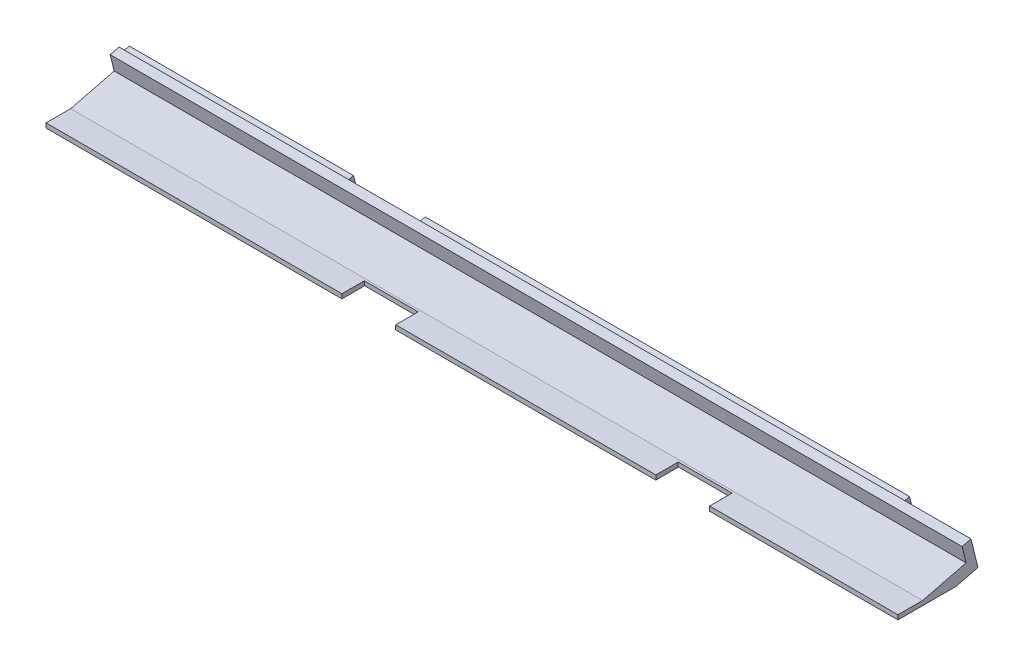
SolidWorks part; units mm, degrees
ref_plane "Front Plane" through (0, 0, 0) normal (0, 0, 1) x (1, 0, 0)
ref_plane "Top Plane" through (0, 0, 0) normal (0, 1, 0) x (1, 0, 0)
ref_plane "Right Plane" through (0, 0, 0) normal (1, 0, 0) x (0, 0, -1)
sketch "Sketch1" plane through (0, 0, 0) normal (1, 0, 0) x (0, 0, -1)
  line L0 (0, 0) -> (13, 0)
  line L1 (0, 0) -> (0, 1)
  line L2 (0, 1) -> (5.5, 1)
  line L3 (5.5, 1) -> (15.203, 3.4192)
  line L4 (13, 0) -> (19.7921, 1.6935)
  line L5 (19.7921, 1.6935) -> (18.5825, 6.5449)
  line L6 (15.203, 3.4192) -> (14.3041, 7.0241)
  line L7 (14.3041, 7.0241) -> (16.279, 7.5165)
  line L8 (16.279, 7.5165) -> (16.6419, 6.0611)
  line L9 (16.6419, 6.0611) -> (18.5825, 6.5449)
  dimension "D1" = 13
  dimension "D2" = 1
  dimension "D3" = 5.5
  dimension "D4" = 10
  dimension "D5" = 194
  dimension "D6" = 7
  dimension "D7" = 5
  dimension "D8" = 1.5
  dimension "D9" = 2
extrude "Profile" add sketch "Sketch1" along normal blind 190
sketch "Sketch2" plane through (0, 4.745, -19.0312) normal (0, 0.2419, -0.9703) x (-1, 0, 0)
  line L0 (-190, -3.145) -> (0, -3.145) construction
  line L1 (-188, -3.145) -> (-2, -3.145)
  line L2 (-188, -3.145) -> (-188, -1.145)
  line L3 (-188, -1.145) -> (-2, -1.145)
  line L4 (-2, -3.145) -> (-2, -1.145)
  line L5 (0, -3.145) -> (0, 1.855) construction
  line L6 (-190, -3.145) -> (-190, 1.855) construction
  dimension "D1" = 2
  dimension "D2" = 2
  dimension "D3" = 2
extrude "Air inlet" cut sketch "Sketch2" against normal through all
sketch "Bottom tab cuts" plane through (0, 1, 0) normal (0, 1, 0) x (1, 0, 0)
  line L0 (190, 0) -> (0, 0) construction
  line L1 (148, 0) -> (136, 0)
  line L2 (148, 0) -> (148, 5)
  line L3 (148, 5) -> (136, 5)
  line L4 (136, 0) -> (136, 5)
  line L5 (190, 5.5) -> (190, 0) construction
  line L8 (78, 0) -> (66, 0)
  line L9 (78, 0) -> (78, 5)
  line L10 (78, 5) -> (66, 5)
  line L11 (66, 0) -> (66, 5)
  dimension "D1" = 42
  dimension "D2" = 12
  dimension "D3" = 5
  dimension "D4" = 112
extrude "Bottom tabs" cut sketch "Bottom tab cuts" against normal blind 14
sketch "Sketch5" plane through (0, 1.7999, 0.4488) normal (0, 0.9703, 0.2419) x (1, 0, 0)
  line L0 (190, 17.6138) -> (0, 17.6138) construction
  line L1 (190, 19.6138) -> (174, 19.6138)
  line L2 (190, 19.6138) -> (190, 17.6138)
  line L3 (190, 17.6138) -> (174, 17.6138)
  line L4 (174, 19.6138) -> (174, 17.6138)
  line L5 (190, 19.6138) -> (0, 19.6138) construction
  line L6 (66, 19.6138) -> (50, 19.6138)
  line L7 (66, 19.6138) -> (66, 17.6138)
  line L8 (66, 17.6138) -> (50, 17.6138)
  line L9 (50, 19.6138) -> (50, 17.6138)
  line L10 (190, 17.6138) -> (0, 17.6138) construction
  dimension "D1" = 16
  dimension "D2" = 124
extrude "Cut-Extrude3" cut sketch "Sketch5" against normal blind 14
